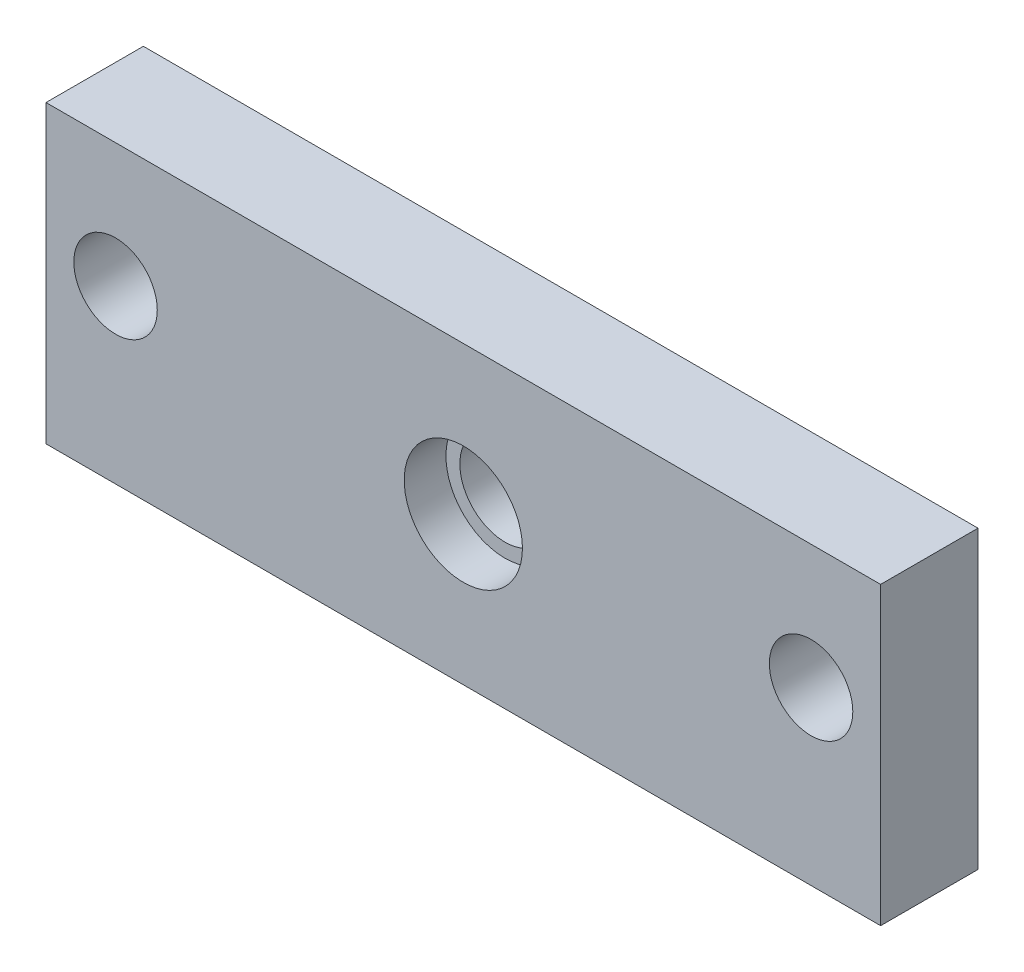
SolidWorks part; units mm, degrees
ref_plane "Front Plane" through (0, 0, 0) normal (0, 0, 1) x (1, 0, 0)
ref_plane "Top Plane" through (0, 0, 0) normal (0, 1, 0) x (1, 0, 0)
ref_plane "Right Plane" through (0, 0, 0) normal (1, 0, 0) x (0, 0, -1)
sketch "Sketch1" plane through (0, 0, 0) normal (0, 0, 1) x (1, 0, 0)
  line L1 (-60, -21.25) -> (60, -21.25)
  line L2 (-60, -21.25) -> (-60, 21.25)
  line L3 (-60, 21.25) -> (60, 21.25)
  line L4 (60, -21.25) -> (60, 21.25)
  line L5 (-60, -21.25) -> (60, 21.25) construction
  line L6 (-60, 21.25) -> (60, -21.25) construction
  point P0 (0, 0)
  dimension "D1" = 120
  dimension "D2" = 42.5
extrude "Boss-Extrude1" add sketch "Sketch1" along normal mid plane 14
sketch "Sketch2" plane through (0, 0, 7) normal (0, 0, 1) x (1, 0, 0)
  circle A0 centre (0, 0) radius 8.5
  dimension "D1" = 17
extrude "Cut-Extrude1" cut sketch "Sketch2" against normal blind 6
sketch "Sketch3" plane through (0, 0, 1) normal (0, 0, 1) x (1, 0, 0)
  circle A0 centre (0, 0) radius 6.5
  dimension "D1" = 13
extrude "Cut-Extrude2" cut sketch "Sketch3" against normal through all
sketch "Sketch5" plane through (0, 0, 7) normal (0, 0, 1) x (1, 0, 0)
  line L0 (-40.6477, 3.4) -> (36.4799, 3.4) construction
  circle A0 centre (-50, 3.4) radius 6
  circle A1 centre (50, 3.4) radius 6
  dimension "D1" = 12
  dimension "D2" = 12
  dimension "D4" = 50
  dimension "D3" = 50
  dimension "D5" = 3.4
extrude "Cut-Extrude4" cut sketch "Sketch5" against normal through all
sketch "Sketch6" plane through (0, -21.25, 0) normal (0, -1, 0) x (1, 0, 0)
  line L0 (-60, 0) -> (60, 0) construction
  line L1 (-60, 7) -> (-60, -7) construction
  line L2 (60, 7) -> (60, -7) construction
  circle A0 centre (-50, 0) radius 2.5
  circle A1 centre (-25, 0) radius 2.5
  circle A2 centre (25, 0) radius 2.5
  circle A3 centre (50, 0) radius 2.5
  circle A4 centre (-37.5, 0) radius 1.25
  circle A5 centre (37.5, 0) radius 1.25
  dimension "D1" = 5
  dimension "D2" = 5
  dimension "D3" = 5
  dimension "D4" = 5
  dimension "D5" = 10
  dimension "D9" = 2.5
  dimension "D10" = 2.5
  dimension "D11" = 22.5
  dimension "D12" = 22.5
  dimension "D6" = 35
  dimension "D7" = 10
  dimension "D8" = 35
extrude "Cut-Extrude5" cut sketch "Sketch6" against normal blind 10
